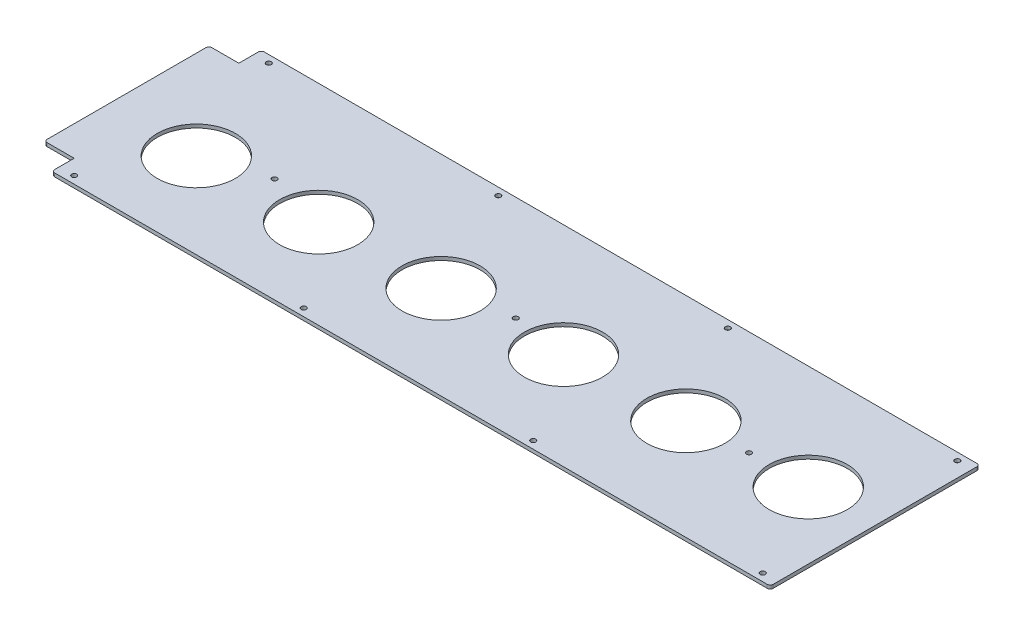
SolidWorks part; units mm, degrees
material "Acrylic (Medium-high impact)"
ref_plane "Front" through (0, 0, 0) normal (0, 0, 1) x (1, 0, 0)
ref_plane "Top" through (0, 0, 0) normal (0, 1, 0) x (1, 0, 0)
ref_plane "Right" through (0, 0, 0) normal (1, 0, 0) x (0, 0, -1)
sketch "Sketch1" plane through (0, 0, 0) normal (0, 1, 0) x (1, 0, 0)
  line L0 (1355.9397, -43.6078) -> (720.9397, -43.6078) construction
  line L5 (1355.9397, 24.9722) -> (1355.9397, -112.1878) construction
  line L6 (720.9397, -112.1878) -> (720.9397, 24.9722) construction
  line L12 (1354.6697, -113.4578) -> (722.2097, -113.4578) construction
  line L13 (746.3397, 45.2922) -> (1355.9397, 45.2922) construction
  line L27 (720.9397, 26.2422) -> (720.9397, -113.4578)
  line L32 (746.3397, -132.5078) -> (1355.9397, -132.5078) construction
  line L44 (1355.9397, 45.2922) -> (1355.9397, -132.5078)
  line L45 (746.3397, 45.2922) -> (1355.9397, -132.5078) construction
  line L50 (746.3397, -132.5078) -> (1355.9397, 45.2922) construction
  line L53 (720.9397, -113.4578) -> (746.3397, -113.4578)
  line L54 (746.3397, -132.5078) -> (746.3397, -113.4578)
  line L58 (720.9397, 26.2422) -> (746.3397, 26.2422)
  line L59 (746.3397, 45.2922) -> (746.3397, 26.2422)
  line L60 (722.2097, 26.2422) -> (1354.6697, 26.2422) construction
  line L61 (1355.9397, -132.5078) -> (746.3397, -132.5078)
  line L62 (1355.9397, 45.2922) -> (746.3397, 45.2922)
  circle A0 centre (1299.3357, -43.6078) radius 33.147
  circle A1 centre (1198.7537, -46.8689) radius 33.147
  circle A2 centre (1098.1718, -50.13) radius 33.147
  circle A3 centre (997.5898, -53.3911) radius 33.147
  circle A4 centre (897.0079, -56.6522) radius 33.147
  circle A5 centre (796.4259, -59.9133) radius 33.147
  circle A6 centre (1299.3357, -43.6078) radius 33.02 construction
  point P6 (1051.1397, -43.6078)
  dimension "D3" = 0.127
  dimension "D1" = 177.8
  dimension "D2" = 25.4
extrude "Boss-Extrude1" add sketch "Sketch1" along normal blind 2.9718
hole_wizard "#8 Clearance Hole1" positions "Sketch2" profile "Sketch3" hole size "#8" standard "ANSI Inch" end condition through all
sketch "Sketch2" plane through (0, 2.9718, 0) normal (0, 1, 0) x (1, 0, 0)
  point P0 (759.0397, 38.9422)
  point P3 (759.0397, -126.1578)
  point P6 (953.773, -126.1578)
  point P9 (953.773, 38.9422)
  point P12 (1148.5063, 38.9422)
  point P15 (1148.5063, -126.1578)
  point P18 (1343.2397, -126.1578)
  point P22 (1343.2397, 38.9422)
  point P26 (1249.0183, -43.6078)
  point P29 (1051.1397, -43.6078)
  point P32 (846.4791, -43.6078)
sketch "Sketch3" plane through (759.0397, 2.9718, -38.9422) normal (1, 0, 0) x (0, 0, 1)
  line L0 (0, 0) -> (0, 2.9718)
  line L1 (0, 2.9718) -> (2.1526, 2.9718)
  line L2 (2.1526, 2.9718) -> (2.1526, 0)
  line L5 (2.1526, 0) -> (0, 0)
  line L11 (0, -6.35) -> (0, 107.95) construction
  dimension "Thru Hole Dia." = 4.3053
  dimension "Thru Hole Depth" = 2.9718
fillet "Fillet1" radius 2.54 6 edges at (720.9397, 1.4859, 113.4578) (720.9397, 1.4859, -26.2422) (746.3397, 1.4859, -45.2922) (746.3397, 1.4859, 132.5078) (1355.9397, 1.4859, 132.5078) (1355.9397, 1.4859, -45.2922)
